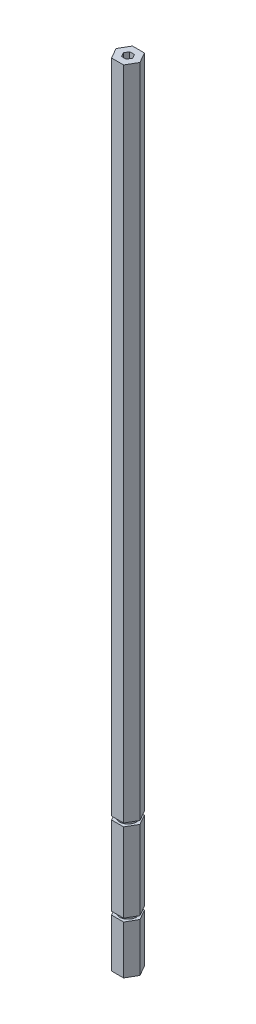
SolidWorks part; units mm, degrees
ref_plane "Front Plane" through (0, 0, 0) normal (0, 0, 1) x (1, 0, 0)
ref_plane "Top Plane" through (0, 0, 0) normal (0, 1, 0) x (1, 0, 0)
ref_plane "Right Plane" through (0, 0, 0) normal (1, 0, 0) x (0, 0, -1)
sketch "Sketch1" plane through (0, 0, 0) normal (0, 1, 0) x (1, 0, 0)
  line L9 (7.3323, 0) -> (3.6662, 6.35)
  line L10 (3.6662, 6.35) -> (-3.6662, 6.35)
  line L11 (-3.6662, 6.35) -> (-7.3323, 0)
  line L12 (-7.3323, 0) -> (-3.6662, -6.35)
  line L13 (-3.6662, -6.35) -> (3.6662, -6.35)
  line L14 (3.6662, -6.35) -> (7.3323, 0)
  line L15 (1.4434, 2.5) -> (-1.4434, 2.5)
  line L16 (-1.4434, 2.5) -> (-2.8868, 0)
  line L17 (-2.8868, 0) -> (-1.4434, -2.5)
  line L18 (-1.4434, -2.5) -> (1.4434, -2.5)
  line L19 (1.4434, -2.5) -> (2.8868, 0)
  line L20 (2.8868, 0) -> (1.4434, 2.5)
  circle A0 centre (0, 0) radius 6.35 construction
  circle A1 centre (0, 0) radius 2.5 construction
  dimension "D1" = 12.7
  dimension "D2" = 5
extrude "Boss-Extrude1" add sketch "Sketch1" along normal blind 482.6
sketch "Sketch3" plane through (0, 0, 0) normal (1, 0, 0) x (0, 0, -1)
  line L0 (0, 482.6) -> (0, 431.8613) construction
  line L2 (0, 482.6) -> (0, 0) construction
  line L7 (-5.0165, 81.915) -> (5.0165, 81.915) construction
  line L10 (5.0165, 81.915) -> (7.5565, 81.915)
  line L11 (5.0165, 81.915) -> (5.0165, 79.883)
  line L12 (5.0165, 79.883) -> (7.5565, 79.883)
  line L13 (7.5565, 81.915) -> (7.5565, 79.883)
  line L14 (0, 0) -> (6.35, 0) construction
  line L15 (5.0165, 79.883) -> (5.0165, 31.623) construction
  line L16 (5.0165, 55.753) -> (-13.2923, 55.753) construction
  line L17 (5.0165, 29.591) -> (7.5565, 29.591)
  line L18 (5.0165, 29.591) -> (5.0165, 31.623)
  line L19 (5.0165, 31.623) -> (7.5565, 31.623)
  line L20 (7.5565, 29.591) -> (7.5565, 31.623)
  point P7 (0, 81.915)
  dimension "D1" = 10.033
  dimension "D2" = 79.883
  dimension "D3" = 2.032
  dimension "D4" = 2.54
  dimension "D5" = 48.26
revolve "Cut-Revolve2" cut sketch "Sketch3" angle 360 about L0
